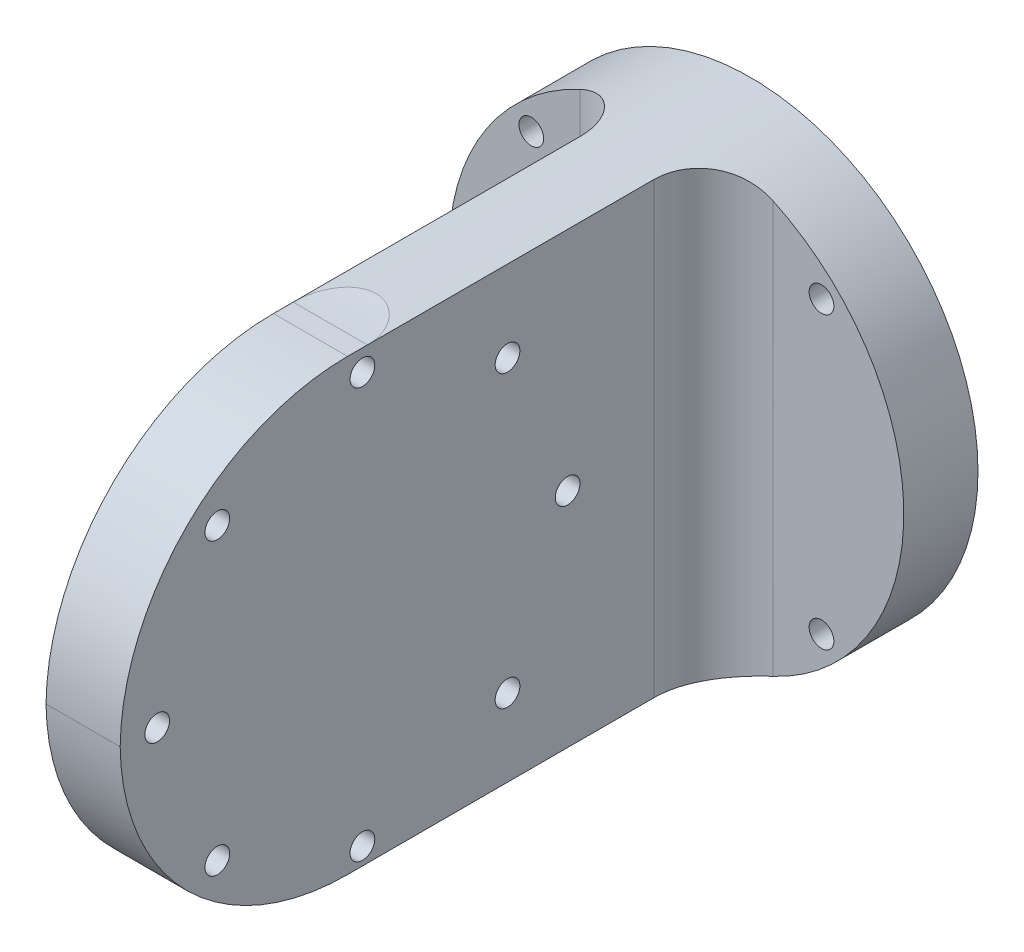
SolidWorks part; units mm, degrees
ref_plane "Front Plane" through (0, 0, 0) normal (0, 0, 1) x (1, 0, 0)
ref_plane "Top Plane" through (0, 0, 0) normal (0, 1, 0) x (1, 0, 0)
ref_plane "Right Plane" through (0, 0, 0) normal (1, 0, 0) x (0, 0, -1)
sketch "Sketch2" plane through (0, 0, 0) normal (0, 0, 1) x (1, 0, 0)
  circle A0 centre (0, 0) radius 46
  dimension "D1" = 92
extrude "Boss-Extrude1" add sketch "Sketch2" along normal blind 15
sketch "Sketch3" plane through (0, 0, 15) normal (0, 0, 1) x (1, 0, 0)
  line L1 (-7.5, 45.3845) -> (7.5, 45.3845)
  line L2 (-7.5, 45.3845) -> (-7.5, -45.3845)
  line L3 (-7.5, -45.3845) -> (7.5, -45.3845)
  line L4 (7.5, 45.3845) -> (7.5, -45.3845)
  line L5 (-7.5, 45.3845) -> (7.5, -45.3845) construction
  line L6 (-7.5, -45.3845) -> (7.5, 45.3845) construction
  circle A0 centre (0, 0) radius 46 construction
  arc A1 (7.5, 45.3845) -> (-7.5, 45.3845) centre (0, 0) ccw
  arc A2 (-7.5, -45.3845) -> (7.5, -45.3845) centre (0, 0) ccw
  point P0 (0, 0)
  dimension "D1" = 15
  dimension "D2" = 90.7689
extrude "Boss-Extrude2" add sketch "Sketch3" along normal blind 120 contours L4 L1 L2 L3 region at (0, 0, 15)
fillet "Fillet1" radius 12 2 edges at (7.5, 0, 15) (-7.5, 0, 15)
sketch "Sketch4" plane through (0, 0, 0) normal (0, 0, -1) x (-1, 0, 0)
  circle A2 centre (29.3449, 29.3449) radius 2.5
  circle A4 centre (29.3449, -29.3449) radius 2.5
  circle A6 centre (-29.3449, -29.3449) radius 2.5
  circle A8 centre (-29.3449, 29.3449) radius 2.5
  point P21 (0, 0)
extrude "Cut-Extrude1" cut sketch "Sketch4" against normal blind 100
fillet "Fillet2" radius 46 2 edges at (0, -45.3845, 135) (0, 45.3845, 135)
sketch "Sketch5" plane through (7.5, 0, 0) normal (1, 0, 0) x (0, 0, -1)
  circle A1 centre (-127.5, -0.393) radius 2.5
  circle A2 centre (-115.3449, 28.9519) radius 2.5
  circle A3 centre (-86, 41.107) radius 2.5
  circle A4 centre (-56.6551, 28.9519) radius 2.5
  circle A5 centre (-44.5, -0.393) radius 2.5
  circle A6 centre (-56.6551, -29.7379) radius 2.5
  circle A7 centre (-86, -41.893) radius 2.5
  circle A8 centre (-115.3449, -29.7379) radius 2.5
  point P21 (-86, -0.393)
  dimension "D2" = 5
  dimension "D3" = 8
extrude "Cut-Extrude2" cut sketch "Sketch5" against normal blind 100
fillet "Fillet3" radius 70 2 edges at (0, -45.3845, 15) (0, 45.3845, 15)
